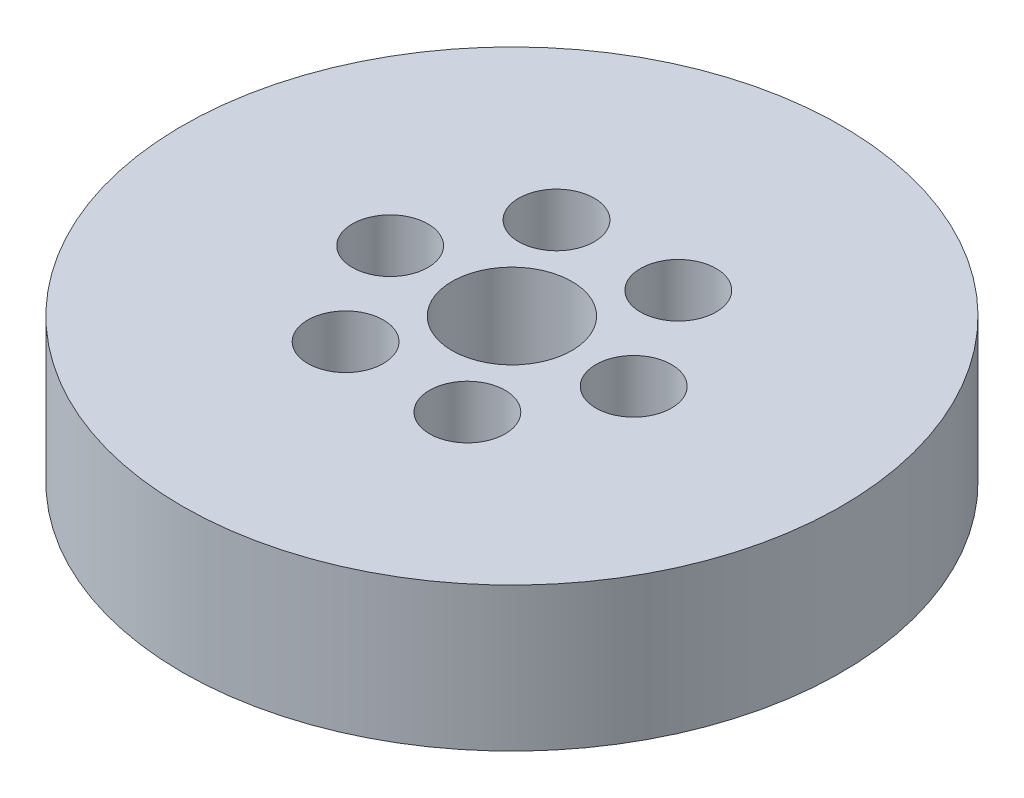
SolidWorks part; units mm, degrees
ref_plane "Front Plane" through (0, 0, 0) normal (0, 0, 1) x (1, 0, 0)
ref_plane "Top Plane" through (0, 0, 0) normal (0, 1, 0) x (1, 0, 0)
ref_plane "Right Plane" through (0, 0, 0) normal (1, 0, 0) x (0, 0, -1)
sketch "Sketch1" plane through (0, 0, 0) normal (0, 1, 0) x (1, 0, 0)
  circle A0 centre (0, 0) radius 55
  dimension "FLANGE_OD" = 110
extrude "Boss-Extrude1" add sketch "Sketch1" along normal blind 24
sketch "Sketch2" plane through (0, 0, 0) normal (0, 1, 0) x (1, 0, 0)
  circle A0 centre (0, 0) radius 10
  dimension "BORE_D" = 20
extrude "Cut-Extrude1" cut sketch "Sketch2" along normal through all
sketch "Sketch3" plane through (0, 24, 0) normal (0, 1, 0) x (1, 0, 0)
  circle A0 centre (0, 0) radius 20.3228 construction
  circle A1 centre (-20.3228, 0) radius 6.3089
  dimension "BOLT_D" = 12.6179
  dimension "BOLT_PCD" = 40.6457
extrude "Cut-Extrude2" cut sketch "Sketch3" against normal blind 17.6729
pattern_circular "CirPattern1" count 6 over 360 about axis through (0, 0, 0) along (0, 1, 0) of "Cut-Extrude2"
